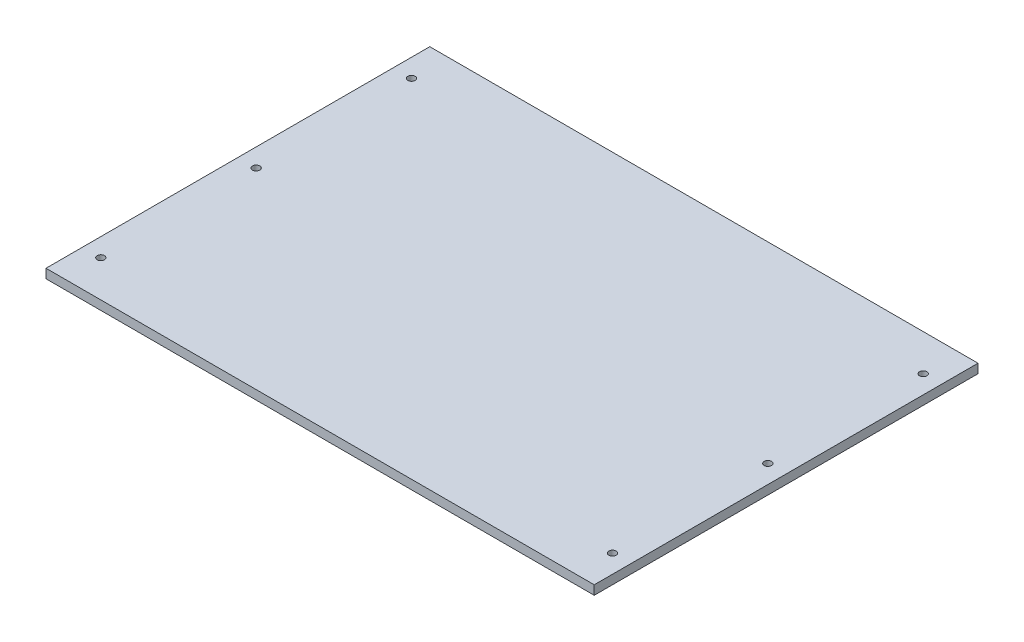
SolidWorks part; units mm, degrees
ref_plane "Front Plane" through (0, 0, 0) normal (0, 0, 1) x (1, 0, 0)
ref_plane "Top Plane" through (0, 0, 0) normal (0, 1, 0) x (1, 0, 0)
ref_plane "Right Plane" through (0, 0, 0) normal (1, 0, 0) x (0, 0, -1)
sketch "Sketch1" plane through (0, 0, 0) normal (0, 1, 0) x (1, 0, 0)
  line L0 (-140, 105) -> (-140, -105) construction
  line L1 (-150, -105) -> (150, -105)
  line L2 (-150, -105) -> (-150, 105)
  line L3 (-150, 105) -> (150, 105)
  line L4 (150, -105) -> (150, 105)
  line L5 (-150, -105) -> (150, 105) construction
  line L6 (-150, 105) -> (150, -105) construction
  line L7 (-2.75, 0) -> (2.75, 0) construction
  line L8 (0, -2.75) -> (0, 2.75) construction
  circle A0 centre (-140, 85) radius 2
  circle A1 centre (-140, -85) radius 2
  circle A2 centre (-140, 0) radius 2
  circle A3 centre (140, -85) radius 2
  circle A4 centre (140, 0) radius 2
  circle A5 centre (140, 85) radius 2
  point P0 (0, 0)
  dimension "D5" = 4
  dimension "D1" = 210
  dimension "D2" = 300
  dimension "D3" = 10
  dimension "D4" = 20
extrude "Boss-Extrude1" add sketch "Sketch1" along normal blind 5
